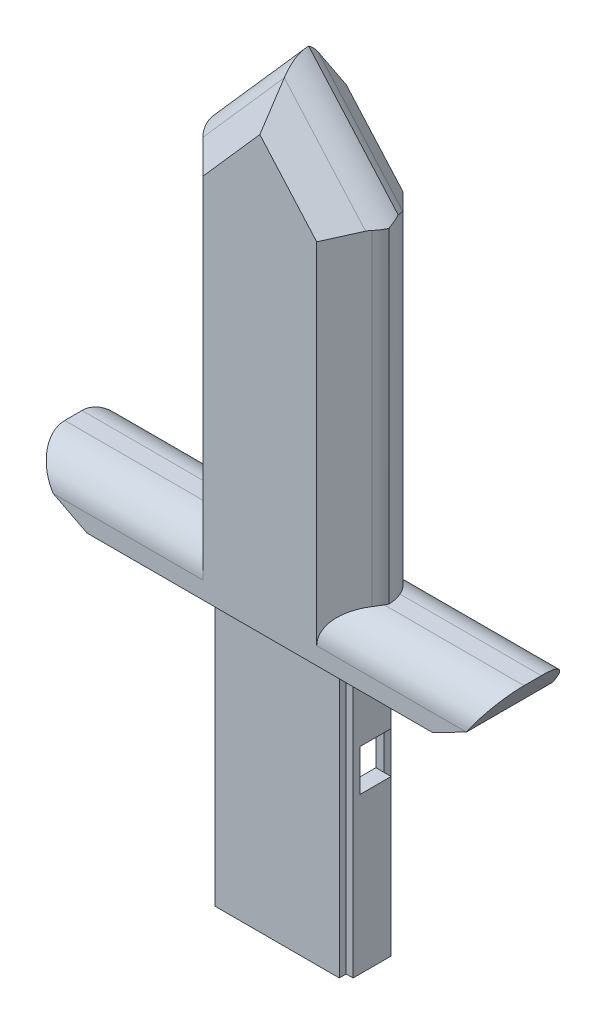
SolidWorks part; units mm, degrees
ref_plane "前视基准面" through (0, 0, 0) normal (0, 0, 1) x (1, 0, 0)
ref_plane "上视基准面" through (0, 0, 0) normal (0, 1, 0) x (1, 0, 0)
ref_plane "右视基准面" through (0, 0, 0) normal (1, 0, 0) x (0, 0, -1)
other "Configuration Table"
sketch "草图1" plane through (0, 0, 0) normal (0, 0, 1) x (1, 0, 0)
  line L0 (0, -55) -> (0, 55) construction
  line L1 (0, 200) -> (-26.4575, 170)
  line L2 (-26.4575, 170) -> (-26.4575, 75)
  line L3 (-26.4575, 75) -> (-66.4575, 75)
  line L4 (-66.4575, 75) -> (-59.7843, 65.0266)
  line L5 (-59.7843, 65.0266) -> (-50, 60)
  line L7 (-50, 60) -> (-20, 60)
  line L9 (-20, 60) -> (-20, -20)
  line L10 (-20, -20) -> (20, -20)
  line L11 (0, 200) -> (0, -20)
  line L15 (-26.4575, 170) -> (26.4575, 170) construction
  line L18 (20, 60) -> (20, -20)
  line L19 (50, 60) -> (20, 60)
  line L20 (59.7843, 65.0266) -> (50, 60)
  line L21 (66.4575, 75) -> (59.7843, 65.0266)
  line L22 (26.4575, 75) -> (66.4575, 75)
  line L23 (26.4575, 170) -> (26.4575, 75)
  line L24 (0, 200) -> (26.4575, 170)
  point P18 (0, 170)
  dimension "D1" = 80
  dimension "D2" = 20
  dimension "D3" = 220
  dimension "D4" = 40
  dimension "D5" = 95
  dimension "D6" = 15
  dimension "D7" = 30
  dimension "D8" = 40
  dimension "D9" = 12
  dimension "D10" = 11
  dimension "D11" = 20
extrude "凸台-拉伸1" add sketch "草图1" along normal blind 15 contours L1 L15 L11 | L11 L15 L24 | L15 L2 L3 L4 L5 L7 L9 L10 L11 | L15 L11 L10 L18 L19 L20 L21 L22 L23
sketch "草图2" plane through (0, 0, 0) normal (0, 0, -1) x (-1, 0, 0)
  line L0 (0, 81.7011) -> (-15, 66.7011)
  line L1 (-15, 66.7011) -> (0, 51.7011)
  line L2 (0, 51.7011) -> (15, 66.7011)
  line L3 (15, 66.7011) -> (0, 81.7011)
  dimension "D1" = 30
  dimension "D4" = 51.7011
extrude "切除-拉伸4" cut sketch "草图2" against normal through all
sketch "草图4" plane through (0, 0, 0) normal (0, 0, -1) x (-1, 0, 0)
  line L0 (-15, 66.7011) -> (-15, -15)
  line L1 (-15, -15) -> (15, -15)
  line L2 (15, -15) -> (15, 66.7011)
  line L3 (20, -20) -> (-20, -20) construction
  line M6 (15, 66.7011) -> (0, 51.7011)
  line M7 (0, 51.7011) -> (-15, 66.7011)
  dimension "D1" = 5
extrude "切除-拉伸5" cut sketch "草图4" against normal blind 5 and the other way through all contours L1 L2 L0 M6 M7
sketch "草图5" plane through (0, 0, 0) normal (0, 0, 1) x (1, 0, 0)
  line L0 (0, 200) -> (26.4575, 170)
  line L1 (26.4575, 170) -> (26.4575, 75)
  line L2 (26.4575, 75) -> (66.4575, 75)
  line L3 (66.4575, 75) -> (59.7843, 65.0266)
  line L4 (59.7843, 65.0266) -> (50, 60)
  line L5 (50, 60) -> (20, 60)
  line L6 (20, 60) -> (-20, 60)
  line L7 (-20, 60) -> (-50, 60)
  line L8 (-50, 60) -> (-59.7843, 65.0266)
  line L9 (-59.7843, 65.0266) -> (-66.4575, 75)
  line L10 (-66.4575, 75) -> (-26.4575, 75)
  line L11 (-26.4575, 75) -> (-26.4575, 170)
  line L12 (-26.4575, 170) -> (0, 200)
extrude "凸台-拉伸2" add sketch "草图5" against normal blind 5
sketch "草图7" plane through (0, 0, 0) normal (0, 0, 1) x (1, 0, 0)
  line L0 (0, 81.7011) -> (-15, 66.7011)
  line L1 (-15, 66.7011) -> (-15, 60)
  line L2 (-15, 60) -> (15, 60) construction
  line L3 (-15, 60) -> (15, 60)
  line L4 (15, 60) -> (15, 66.7011)
  line L5 (15, 66.7011) -> (0, 81.7011)
extrude "切除-拉伸6" cut sketch "草图7" against normal blind 5
sketch "草图8" plane through (0, 0, 5) normal (0, 0, -1) x (-1, 0, 0)
  line L0 (-15, 66.7011) -> (0, 51.7011)
  line L1 (0, 51.7011) -> (15, 66.7011)
  line L2 (15, 66.7011) -> (15, -15)
  line L3 (15, -15) -> (-15, -15)
  line L4 (-15, -15) -> (-15, 66.7011)
extrude "切除-拉伸7" cut sketch "草图8" against normal blind 5
sketch "草图9" plane through (0, -20, 0) normal (0, -1, 0) x (1, 0, 0)
  line L0 (15, 4) -> (15, 7)
  line L1 (15, 7) -> (-15, 7)
  line L2 (-15, 7) -> (-15, 4)
  line L3 (-15, 4) -> (15, 4)
  line L4 (-20, 0) -> (20, 0) construction
  line L5 (20, 15) -> (20, 0) construction
  line L6 (-20, 15) -> (-20, 0) construction
  line L7 (-20, 15) -> (20, 15) construction
  dimension "D1" = 4
  dimension "D2" = 5
  dimension "D3" = 5
  dimension "D4" = 8
extrude "切除-拉伸8" cut sketch "草图9" against normal blind 5
sketch "草图10" plane through (0, 0, -5) normal (0, 0, -1) x (-1, 0, 0)
  line L0 (-15, 66.7011) -> (-15, 116.7011)
  line L1 (-15, 116.7011) -> (15, 116.7011)
  line L2 (15, 116.7011) -> (15, 66.7011)
  line L3 (15, 66.7011) -> (-15, 66.7011)
  dimension "D1" = 50
extrude "切除-拉伸9" cut sketch "草图10" against normal up to surface (15 mm away) up to face at (0, 31.0207, 10)
sketch "草图11" plane through (0, 60, 0) normal (0, -1, 0) x (1, 0, 0)
  line L0 (17.5, -1.5) -> (15, -1.5)
  line L2 (15, -5) -> (15, 0) construction
  line L3 (15, -1.5) -> (15, -5)
  line L4 (15, -5) -> (-15, -5)
  line L5 (-15, -5) -> (-15, -1.5)
  line L6 (-15, -5) -> (-15, 0) construction
  line L7 (-15, -1.5) -> (-17.5, -1.5)
  line L8 (-17.5, -1.5) -> (-17.5, 0)
  line L9 (-20, 0) -> (-15, 0) construction
  line L10 (-17.5, 0) -> (17.5, 0)
  line L11 (17.5, 0) -> (17.5, -1.5)
  dimension "D1" = 1.5
  dimension "D2" = 1.5
  dimension "D3" = 2.5
  dimension "D4" = 2.5
extrude "切除-拉伸10" cut sketch "草图11" against normal up to surface (56.7011 mm away) up to face at (0, 116.7011, 2.5)
sketch "草图12" plane through (0, 0, 10) normal (0, 0, -1) x (-1, 0, 0)
sketch "草图13" plane through (0, 0, 10) normal (0, 0, -1) x (-1, 0, 0)
  line L0 (-20, 121.7011) -> (-20, 71.7011)
  line L1 (-20, 71.7011) -> (20, 71.7011)
  line L2 (20, 71.7011) -> (20.5279, 121.7011)
  line L3 (20.5279, 121.7011) -> (-20, 121.7011)
  dimension "D1" = 40
  dimension "D2" = 50
  dimension "D3" = 10
  dimension "D4" = 20
extrude "切除-拉伸11" cut sketch "草图13" along normal blind 7
sketch "草图14" plane through (0, 0, -5) normal (0, 0, -1) x (-1, 0, 0)
  line L0 (15, 116.7011) -> (-15, 116.7011) construction
  line L1 (-15.6, 116.7011) -> (15.6, 116.7011)
  line L2 (-15.6, 116.7011) -> (-15.6, -14.9949)
  line L3 (-15.6, -14.9949) -> (15.6, -14.9949)
  line L4 (15.6, 116.7011) -> (15.6, -14.9949)
  line L5 (-15, 60) -> (-15, 116.7011) construction
  line L6 (15, 116.7011) -> (15, 60) construction
  dimension "D1" = 0.6
  dimension "D2" = 0.6
  dimension "D3" = 131.6961
extrude "切除-拉伸12" cut sketch "草图14" against normal up to surface (15 mm away) up to face at (0, 31.0207, 10)
sketch "草图15" plane through (0, 71.7011, 0) normal (0, 1, 0) x (1, 0, 0)
  line L0 (-20, -10) -> (20, -10)
  line L1 (-20, -10) -> (-20, -3)
  line L2 (-20, -3) -> (-20, -10) construction
  line L3 (-20, -3) -> (20, -3)
  line L4 (20, -3) -> (20, -10)
  dimension "D1" = 7
extrude "切除-拉伸14" cut sketch "草图15" against normal blind 9
sketch "草图16" plane through (0, 0, 10) normal (0, 0, -1) x (-1, 0, 0)
  line L0 (0, 83.1153) -> (-16.4142, 66.7011)
  line L1 (-16.4142, 66.7011) -> (0, 50.2869)
  line L2 (0, 50.2869) -> (16.4142, 66.7011)
  line L3 (16.4142, 66.7011) -> (0, 83.1153)
  line L4 (-15, 66.7011) -> (0, 81.7011) construction
  line L5 (0, 81.7011) -> (15, 66.7011) construction
  line L6 (15, 66.7011) -> (0, 51.7011) construction
  line L7 (0, 51.7011) -> (-15, 66.7011) construction
  dimension "D1" = 1
  dimension "D2" = 1
  dimension "D3" = 1
  dimension "D4" = 1
extrude "切除-拉伸15" cut sketch "草图16" against normal through all
sketch "草图17" plane through (0, 0, 15) normal (0, 0, 1) x (1, 0, 0)
  line L0 (0, 83.1153) -> (-16.4142, 66.7011)
  line L1 (-16.4142, 66.7011) -> (0, 50.2869)
  line L2 (0, 50.2869) -> (16.4142, 66.7011)
  line L3 (16.4142, 66.7011) -> (0, 83.1153)
extrude "凸台-拉伸3" add sketch "草图17" against normal up to surface (5 mm away) up to face at (0, 66.7011, 10)
sketch "草图18" plane through (0, 0, 15) normal (0, 0, 1) x (1, 0, 0)
  line L0 (-20, 60) -> (20, 60)
  line L1 (20, 60) -> (20, -20)
  line L2 (20, -20) -> (-20, -20)
  line L3 (-20, -20) -> (-20, 60)
sketch "草图19" plane through (0, 0, 15) normal (0, 0, 1) x (1, 0, 0)
  line L0 (-26.4575, 75) -> (26.4575, 75)
  line L1 (0, 200) -> (0, 75)
sketch "草图23" plane through (-26.4575, 0, 0) normal (-1, 0, 0) x (0, 0, 1)
  line L0 (-5, 75) -> (15, 75)
  line L1 (5, 75) -> (5, 82.7603) construction
sketch "草图24" plane through (26.4575, 0, 0) normal (1, 0, 0) x (0, 0, -1)
  line L0 (-15, 75) -> (5, 75)
  line L1 (-5, 75) -> (-5, 85.0123) construction
sketch "草图26" plane through (0, 0, 15) normal (0, 0, 1) x (1, 0, 0)
  line L0 (0, 200) -> (-26.4575, 170)
  line L1 (-26.4575, 170) -> (-26.4575, 75)
  line L2 (-26.4575, 75) -> (-66.4575, 75)
  line L3 (-66.4575, 75) -> (-59.7843, 65.0266)
  line L4 (-59.7843, 65.0266) -> (-50, 60)
  line L5 (-50, 60) -> (-20, 60)
  line L6 (-20, 60) -> (50, 60)
  line L7 (50, 60) -> (59.7843, 65.0266)
  line L8 (59.7843, 65.0266) -> (66.4575, 75)
  line L9 (66.4575, 75) -> (26.4575, 75)
  line L10 (26.4575, 75) -> (26.4575, 170)
  line L11 (26.4575, 170) -> (0, 200)
extrude "凸台-拉伸4" add sketch "草图26" along normal blind 5
sketch "草图27" plane through (0, -20, 0) normal (0, -1, 0) x (1, 0, 0)
  line L2 (-20, 15) -> (-18, 15)
  line L3 (20, 15) -> (-20, 15) construction
  line L4 (-18, 15) -> (-18, 13)
  line L5 (-18, 13) -> (-20, 13)
  line L6 (-20, 15) -> (-20, 0) construction
  line L7 (-20, 13) -> (-20, 15)
  line L8 (-20, 0) -> (-18, 0)
  line L9 (-20, 0) -> (20, 0) construction
  line L10 (-18, 0) -> (-18, 2)
  line L11 (-18, 2) -> (-20, 2)
  line L12 (-20, 2) -> (-20, 0)
  line L13 (20, 15) -> (20, 13)
  line L14 (20, 15) -> (20, 0) construction
  line L15 (20, 13) -> (18, 13)
  line L16 (18, 13) -> (18, 15)
  line L17 (18, 15) -> (20, 15)
  line L18 (20, 0) -> (18, 0)
  line L19 (18, 0) -> (18, 2)
  line L20 (18, 2) -> (20, 2)
  line L21 (20, 2) -> (20, 0)
  dimension "D1" = 2
  dimension "D2" = 2
  dimension "D3" = 2
  dimension "D4" = 2
  dimension "D5" = 2
  dimension "D6" = 2
  dimension "D7" = 2
  dimension "D8" = 2
extrude "切除-拉伸17" cut sketch "草图27" against normal blind 80
sketch "草图29" plane through (0, -20, 0) normal (0, -1, 0) x (-1, 0, 0)
  line L0 (15, -7) -> (15, -4)
  line L1 (15, -4) -> (-15, -4)
  line L2 (-15, -4) -> (-15, -7)
  line L3 (-15, -7) -> (15, -7)
extrude "凸台-拉伸5" add sketch "草图29" against normal up to surface (5 mm away) up to face at (0, -15, 8.5)
sketch "草图30" plane through (15.6, 0, 0) normal (-1, 0, 0) x (0, 0, 1)
  line L0 (2, 25.0051) -> (10, 25.0051)
  line L2 (10, -14.9949) -> (10, 62.7011) construction
  line L3 (10, 25.0051) -> (10, 37.0051)
  line L4 (10, 37.0051) -> (2, 37.0051)
  line L5 (2, 37.0051) -> (2, 25.0051)
  line L6 (10, -14.9949) -> (0, -14.9949) construction
  dimension "D1" = 40
  dimension "D2" = 12
  dimension "D3" = 8
extrude "切除-拉伸19" cut sketch "草图30" against normal up to surface (4.4 mm away) up to face at (20, 20, 7.5)
sketch "草图31" plane through (15.6, 0, 0) normal (-1, 0, 0) x (0, 0, 1)
  line L0 (10, 35.0051) -> (2, 35.0051)
  line L1 (10, 37.0051) -> (10, 62.7011) construction
  line L2 (2, 35.0051) -> (2, 44.0051)
  line L3 (2, 44.0051) -> (10, 44.0051)
  line L4 (10, 44.0051) -> (10, 35.0051)
  line L5 (10, -14.9949) -> (0, -14.9949) construction
  dimension "D1" = 8
  dimension "D2" = 50
  dimension "D3" = 9
sketch "草图32" plane through (0, 60, 0) normal (0, -1, 0) x (1, 0, 0)
  line L0 (-18, 15) -> (18, 15) construction
  line L1 (-22.4, 17.4) -> (22.4, 17.4)
  line L2 (-22.4, 17.4) -> (-22.4, -2.4)
  line L3 (-22.4, -2.4) -> (22.4, -2.4)
  line L4 (22.4, 17.4) -> (22.4, -2.4)
  line L5 (-20, 13) -> (-20, 2) construction
  dimension "D1" = 44.8
  dimension "D2" = 19.8
  dimension "D3" = 2.4
  dimension "D4" = 2.4
extrude "切除-拉伸21" cut sketch "草图32" against normal blind 5
sketch "草图35" plane through (0, 65, 0) normal (0, -1, 0) x (1, 0, 0)
  line L0 (-50, 20) -> (50, 20)
  line L1 (50, 20) -> (50, -5)
  line L2 (50, -5) -> (-50, -5)
  line L3 (-50, -5) -> (-50, 20)
  line L5 (25, -1.5) -> (-25, -1.5)
  line L6 (25, -1.5) -> (25, 16.5)
  line L7 (25, 16.5) -> (-25, 16.5)
  line L8 (-25, -1.5) -> (-25, 16.5)
  line L11 (20, 10) -> (20, 3) construction
  line L13 (15.5816, -5) -> (15.6, -1.5)
  line L14 (-15.6, -5) -> (-15.6, -1.5)
  line M6 (-15.6, -5) -> (-15.6, -1.5)
  line M7 (-15.6, -1.5) -> (-17.5, -1.5)
  line M27 (17.5, -1.5) -> (15.6, -1.5)
  line M28 (15.6, -1.5) -> (15.6, -5)
  line M29 (15.6, -5) -> (50, -5)
  line M30 (50, -5) -> (50, 20)
  line M31 (50, 20) -> (-50, 20)
  line M32 (-50, 20) -> (-50, -5)
  line M33 (-50, -5) -> (-15.6, -5)
  dimension "D1" = 18
  dimension "D2" = 3.5
  dimension "D3" = 50
  dimension "D4" = 5
extrude "凸台-拉伸7" add sketch "草图35" along normal blind 5 contours L5 L8 L7 L6 M27 M28 M29 M30 M31 M32 M33 M6 M7
sketch "草图36" plane through (0, 65, 0) normal (0, -1, 0) x (1, 0, 0)
  line L0 (25, -1.5) -> (25, 16.5)
  line L1 (25, 16.5) -> (-25, 16.5)
  line L2 (-25, 16.5) -> (-25, -1.5)
  line L3 (-25, -1.5) -> (25, -1.5)
  line M1 (-25, 16.5) -> (-25, -1.5)
  line M2 (-25, -1.5) -> (-17.5, -1.5)
  line M3 (-17.5, -1.5) -> (-17.5, 0)
  line M4 (-17.5, 0) -> (-18, 0)
  line M5 (-18, 0) -> (-18, 2)
  line M6 (-18, 2) -> (-20, 2)
  line M7 (-20, 2) -> (-20, 3)
  line M8 (-20, 3) -> (-20, 10)
  line M9 (-20, 10) -> (-20, 13)
  line M10 (-20, 13) -> (-18, 13)
  line M11 (-18, 13) -> (-18, 15)
  line M12 (-18, 15) -> (18, 15)
  line M13 (18, 15) -> (18, 13)
  line M14 (18, 13) -> (20, 13)
  line M15 (20, 13) -> (20, 10)
  line M16 (20, 10) -> (20, 3)
  line M17 (20, 3) -> (20, 2)
  line M18 (20, 2) -> (18, 2)
  line M19 (18, 2) -> (18, 0)
  line M20 (18, 0) -> (17.5, 0)
  line M21 (17.5, 0) -> (17.5, -1.5)
  line M22 (17.5, -1.5) -> (25, -1.5)
  line M23 (25, -1.5) -> (25, 16.5)
  line M24 (25, 16.5) -> (-25, 16.5)
extrude "凸台-拉伸9" add sketch "草图36" along normal blind 2 contours M24 M1 M2 M3 M4 M5 M6 M7 M8 M9 M10 M11 M12 M13 M14 M15 M16 M17 M18 M19 M20 M21 M22 M23
sketch "草图37" plane through (0, 63, 0) normal (0, -1, 0) x (-1, 0, 0)
  line L0 (25, -16.5) -> (25, 1.5) construction
  line L1 (-25, -16.5) -> (25, -16.5) construction
  line L2 (25, 1.5) -> (17.5, 1.5) construction
  line L3 (-25, 1.5) -> (-25, -16.5) construction
  line L4 (-25, -16.5) -> (25, -16.5) construction
  line L5 (-17.5, 1.5) -> (-25, 1.5) construction
  circle A0 centre (22.5, -14) radius 1.2
  circle A1 centre (-22.5, -14) radius 1.2
  circle A2 centre (-22.5, -1) radius 1.2
  circle A3 centre (22.5, -1) radius 1.2
  dimension "D1" = 2.4
  dimension "D4" = 2.4
  dimension "D10" = 2.4
  dimension "D11" = 2.4
  dimension "D2" = 2.5
  dimension "D3" = 2.5
  dimension "D5" = 2.5
  dimension "D6" = 2.5
  dimension "D7" = 2.5
  dimension "D8" = 2.5
  dimension "D9" = 2.5
  dimension "D12" = 2.5
chamfer "倒角1" distance 10 angle 45 1 edges at (-13.2288, 185, -5)
chamfer "倒角2" distance 10 angle 45 1 edges at (16.5621, 181.2204, -5)
chamfer "倒角3" distance 10 angle 45 1 edges at (13.2288, 185, 20)
chamfer "倒角4" distance 10 angle 45 1 edges at (-16.5621, 181.2204, 20)
chamfer "倒角5" distance 10 angle 45 1 edges at (26.4575, 114.9407, 20)
chamfer "倒角6" distance 10 angle 45 1 edges at (26.4575, 114.9407, -5)
chamfer "倒角7" distance 10 angle 45 1 edges at (-26.4575, 114.9407, -5)
chamfer "倒角8" distance 10 angle 45 1 edges at (-26.4575, 114.9407, 20)
fillet "圆角7" radius 10 1 edges at (41.4575, 75, 20)
fillet "圆角8" radius 10 1 edges at (41.4575, 75, -5)
fillet "圆角9" radius 10 1 edges at (-41.4575, 75, -5)
fillet "圆角10" radius 10 1 edges at (-41.4575, 75, 20)
fillet "圆角11" radius 10 1 edges at (26.4575, 122.5, 5)
fillet "圆角12" radius 10 1 edges at (26.4575, 122.5, 10)
fillet "圆角14" radius 10 1 edges at (13.0034, 185.2555, 10)
fillet "圆角15" radius 10 1 edges at (12.7797, 185.5092, 5)
fillet "圆角16" radius 10 1 edges at (-13.5282, 184.6605, 10)
fillet "圆角17" radius 10 1 edges at (-13.379, 184.8296, 5)
fillet "圆角18" radius 10 1 edges at (-26.4575, 121.821, 10)
fillet "圆角19" radius 10 1 edges at (-26.4575, 122.1593, 5)
sketch "草图38" plane through (0, 0, 10) normal (0, 0, -1) x (-1, 0, 0)
  line L2 (15.6, 62.7011) -> (15.6, -14.9949) construction
  line L3 (-15, -15) -> (15, -15) construction
  circle A0 centre (-11.9, 20.2) radius 1.2
  circle A1 centre (12.3, 20.2) radius 1.2
  circle A2 centre (12.3, 57) radius 1.2
  circle A3 centre (-11.9, 57) radius 1.2
  dimension "D1" = 2.4
  dimension "D2" = 2.4
  dimension "D3" = 2.4
  dimension "D4" = 2.4
  dimension "D5" = 24.2
  dimension "D6" = 24.2
  dimension "D7" = 3.3
  dimension "D8" = 3.3
  dimension "D9" = 35.2
  dimension "D10" = 35.2
  dimension "D11" = 72
  dimension "D12" = 72
extrude "切除-拉伸23" cut sketch "草图38" against normal blind 3
sketch "草图39" plane through (0, 0, 10) normal (0, 0, -1) x (-1, 0, 0)
  line L0 (-15.6, -14.9949) -> (-15.6, 81.8297)
  line L1 (-15.6, 81.8297) -> (15.6, 81.8297)
  line L2 (15.6, 81.8297) -> (15.6, -14.9949)
  line L3 (15.6, -14.9949) -> (-15.6, -14.9949)
sketch "草图40" plane through (0, 121.7011, 0) normal (0, -1, 0) x (1, 0, 0)
  line L1 (-25.4676, 12.5781) -> (26.0169, 12.5781)
  line L2 (-25.4676, 12.5781) -> (-25.4676, 0.933)
  line L3 (-25.4676, 0.933) -> (26.0169, 0.933)
  line L4 (26.0169, 12.5781) -> (26.0169, 0.933)
  line M5 (20, 10) -> (-20.5279, 10)
  line M6 (-20.5279, 10) -> (-20.5279, 3)
  line M7 (-20.5279, 3) -> (20, 3)
  line M8 (20, 3) -> (20, 10)
extrude "切除-拉伸24" cut sketch "草图40" against normal blind 8 contours M8 M5 M6 M7
sketch "草图41" plane through (0, 116.7011, 0) normal (0, -1, 0) x (1, 0, 0)
  line L1 (21.831, -9.4178) -> (-23.2428, -9.4178)
  line L2 (21.831, -9.4178) -> (21.831, 6.3066)
  line L3 (21.831, 6.3066) -> (-23.2428, 6.3066)
  line L4 (-23.2428, -9.4178) -> (-23.2428, 6.3066)
  line M5 (-15.6, -5) -> (15.6, -5)
  line M6 (15.6, -5) -> (15.6, -1.5)
  line M7 (15.6, -1.5) -> (17.5, -1.5)
  line M8 (17.5, -1.5) -> (17.5, 0)
  line M9 (17.5, 0) -> (15.6, 0)
  line M10 (15.6, 0) -> (15.6, 3)
  line M11 (15.6, 3) -> (-15.6, 3)
  line M12 (-15.6, 3) -> (-15.6, 0)
  line M13 (-15.6, 0) -> (-17.5, 0)
  line M14 (-17.5, 0) -> (-17.5, -1.5)
  line M15 (-17.5, -1.5) -> (-15.6, -1.5)
  line M16 (-15.6, -1.5) -> (-15.6, -5)
extrude "切除-拉伸25" cut sketch "草图41" against normal blind 46 contours M16 M5 M6 M7 M8 M9 M10 M11 M12 M13 M14 M15
sketch "草图42" plane through (0, 129.7011, 0) normal (0, -1, 0) x (1, 0, 0)
  line L1 (-35.652, 24.0881) -> (44.2679, 24.0881)
  line L2 (-35.652, 24.0881) -> (-35.652, -20.2789)
  line L3 (-35.652, -20.2789) -> (44.2679, -20.2789)
  line L4 (44.2679, 24.0881) -> (44.2679, -20.2789)
  line M5 (20, 3) -> (20, 10)
  line M6 (20, 10) -> (-20.5279, 10)
  line M7 (-20.5279, 10) -> (-20.5279, 3)
  line M8 (-20.5279, 3) -> (-15.6, 3)
  line M9 (-15.6, 3) -> (15.6, 3)
  line M10 (15.6, 3) -> (20, 3)
extrude "切除-拉伸26" cut sketch "草图42" against normal up to surface (33 mm away) contours M10 M5 M6 M7 M8 M9 up to face at (0, 162.7011, -0.8333)
sketch "草图43" plane through (0, 0, 10) normal (0, 0, -1) x (-1, 0, 0)
  line L0 (-15.6, 15.2) -> (15.6, 15.2)
  line L1 (-10.6, 106.2) -> (10.6, 106.2)
  line L2 (-10.6, 106.2) -> (-10.6, 84.2)
  line L3 (-10.6, 84.2) -> (10.6, 84.2)
  line L4 (10.6, 106.2) -> (10.6, 84.2)
  line L5 (-15.6, -14.9949) -> (-15.6, 25.0051) construction
  line L6 (15.6, 62.7011) -> (15.6, -14.9949) construction
  line L7 (-15.6, 37.0051) -> (-15.6, 62.7011) construction
  circle A0 centre (-11.9, 20.2) radius 1.2 construction
  dimension "D1" = 5
  dimension "D2" = 69
  dimension "D3" = 91
  dimension "D4" = 5
  dimension "D5" = 5
extrude "切除-拉伸27" cut sketch "草图43" against normal up to surface (10 mm away) contours L4 L1 L2 L3 up to face at (0, 99.7025, 20)
sketch "草图46" plane through (0, 60, 0) normal (0, -1, 0) x (1, 0, 0)
  line L1 (-27.4, 17.4) -> (27.4, 17.4)
  line L2 (-27.4, 17.4) -> (-27.4, -2.4)
  line L3 (-27.4, -2.4) -> (27.4, -2.4)
  line L4 (27.4, 17.4) -> (27.4, -2.4)
  line L6 (-20, 10) -> (-20, 13) construction
  line L8 (-18, 15) -> (18, 15) construction
  line M5 (-15.6, -1.5) -> (-25, -1.5)
  line M6 (-25, -1.5) -> (-25, 16.5)
  line M7 (-25, 16.5) -> (25, 16.5)
  line M8 (25, 16.5) -> (25, -1.5)
  line M9 (25, -1.5) -> (15.6, -1.5)
  line M10 (15.6, -1.5) -> (15.6, -5)
  line M16 (-15.6, -5) -> (-15.6, -1.5)
  dimension "D1" = 19.8
  dimension "D2" = 54.8
  dimension "D3" = 7.4
  dimension "D4" = 2.4
extrude "切除-拉伸28" cut sketch "草图46" against normal up to surface (3 mm away) contours L4 L1 L2 L3 M16 M5 M6 M7 M8 M9 M10 up to face at (0, 63, 5.9583)
sketch "草图47" plane through (0, 63, 0) normal (0, -1, 0) x (1, 0, 0)
  line L0 (27.4, 17.4) -> (-27.4, 17.4) construction
  line L1 (-27.4, -2.4) -> (-27.4, 17.4) construction
  line L3 (-15.6, -2.4) -> (-27.4, -2.4) construction
  line L4 (27.4, -2.4) -> (27.4, 17.4) construction
  line L5 (27.4, -2.4) -> (15.6, -2.4) construction
  line L6 (27.4, 17.4) -> (27.4, -2.4) construction
  circle A0 centre (-24.9, 14.9) radius 1.2
  circle A1 centre (24.9, 14.9) radius 1.2
  circle A2 centre (24.9, 0.1) radius 1.2
  circle A3 centre (-24.9, 0.1) radius 1.2
  dimension "D3" = 2.4
  dimension "D6" = 2.4
  dimension "D9" = 2.4
  dimension "D12" = 2.4
  dimension "D1" = 2.5
  dimension "D2" = 2.5
  dimension "D4" = 2.5
  dimension "D5" = 2.5
  dimension "D7" = 2.5
  dimension "D8" = 2.5
  dimension "D10" = 2.5
  dimension "D11" = 2.5
extrude "切除-拉伸29" cut sketch "草图47" against normal blind 3
sketch "草图48" plane through (0, 62.7011, 0) normal (0, 1, 0) x (1, 0, 0)
  line L1 (-26.5409, 2.5519) -> (32.582, 2.5519)
  line L2 (-26.5409, 2.5519) -> (-26.5409, -20.82)
  line L3 (-26.5409, -20.82) -> (32.582, -20.82)
  line L4 (32.582, 2.5519) -> (32.582, -20.82)
  line M1 (-15.6, -3) -> (-20, -3)
  line M2 (-20, -3) -> (-20, -10)
  line M3 (-20, -10) -> (-15.6, -10)
  line M4 (-15.6, -10) -> (-15.6, -3)
extrude "凸台-拉伸10" add sketch "草图48" along normal blind 9 contours M4 M1 M2 M3
sketch "草图49" plane through (0, 62.7011, 0) normal (0, 1, 0) x (1, 0, 0)
  line L1 (8.4178, 4.2355) -> (27.2342, 4.2355)
  line L2 (8.4178, 4.2355) -> (8.4178, -17.2548)
  line L3 (8.4178, -17.2548) -> (27.2342, -17.2548)
  line L4 (27.2342, 4.2355) -> (27.2342, -17.2548)
  line M1 (15.6, -10) -> (20, -10)
  line M2 (20, -10) -> (20, -3)
  line M3 (20, -3) -> (15.6, -3)
  line M4 (15.6, -3) -> (15.6, -10)
extrude "凸台-拉伸11" add sketch "草图49" along normal blind 9 contours M4 M1 M2 M3
sketch "草图50" plane through (0, 0, 10) normal (0, 0, -1) x (-1, 0, 0)
  line L1 (-63.6393, 193.626) -> (75.0944, 193.626)
  line L2 (-63.6393, 193.626) -> (-63.6393, -29.1115)
  line L3 (-63.6393, -29.1115) -> (75.0944, -29.1115)
  line L4 (75.0944, 193.626) -> (75.0944, -29.1115)
  circle M5 centre (-11.9, 57) radius 1.2
  circle M6 centre (12.3, 57) radius 1.2
  circle M7 centre (12.3, 20.2) radius 1.2
  circle M8 centre (-11.9, 20.2) radius 1.2
  line M9 (-10.6, 106.2) -> (10.6, 106.2)
  line M10 (10.6, 106.2) -> (10.6, 84.2)
  line M11 (10.6, 84.2) -> (-10.6, 84.2)
  line M12 (-10.6, 84.2) -> (-10.6, 106.2)
  line M13 (-20, 71.7011) -> (-15.6, 71.7011)
  line M14 (-15.6, 71.7011) -> (-15.6, 37.0051)
  line M15 (-15.6, 37.0051) -> (-20, 37.0051)
  line M16 (-20, 37.0051) -> (-20, 25.0051)
  line M17 (-20, 25.0051) -> (-15.6, 25.0051)
  line M18 (-15.6, 25.0051) -> (-15.6, -14.9949)
  line M19 (-15.6, -14.9949) -> (-15, -14.9949)
  line M20 (-15, -14.9949) -> (-15, -15)
  line M21 (-15, -15) -> (15, -15)
  line M22 (15, -15) -> (15, -14.9949)
  line M23 (15, -14.9949) -> (15.6, -14.9949)
  line M24 (15.6, -14.9949) -> (15.6, 71.7011)
  line M25 (15.6, 71.7011) -> (20, 71.7011)
  line M26 (20, 71.7011) -> (20.5279, 121.7011)
  line M27 (20.5279, 121.7011) -> (20.5279, 162.7011)
  line M28 (20.5279, 162.7011) -> (-20, 162.7011)
  line M29 (-20, 162.7011) -> (-20, 71.7011)
extrude "切除-拉伸30" cut sketch "草图50" against normal blind 1 contours M29 M13 M14 M15 M16 M17 M18 M19 M20 M21 M22 M23 M24 M25 M26 M27 M28 M6 M8 M12 M9 M10 M11 M7 M5
sketch "草图52" plane through (0, 0, 20) normal (0, 0, 1) x (1, 0, 0)
  line L0 (-2.5, 99.2) -> (-2.5, 91.2)
  line L1 (-2.5, 91.2) -> (2.5, 91.2)
  line L2 (2.5, 91.2) -> (2.5, 99.2)
  line L3 (2.5, 99.2) -> (-2.5, 99.2)
  line L6 (10.6, 106.2) -> (-10.6, 106.2) construction
  line L7 (-10.6, 106.2) -> (-10.6, 84.2) construction
  line M12 (10.6, 84.2) -> (-10.6, 84.2)
  line M13 (-10.6, 84.2) -> (-10.6, 106.2)
  line M14 (-10.6, 106.2) -> (10.6, 106.2)
  line M15 (10.6, 106.2) -> (10.6, 84.2)
  dimension "D1" = 5
  dimension "D2" = 8
  dimension "D3" = 7
  dimension "D4" = 8.1
extrude "凸台-拉伸12" add sketch "草图52" against normal blind 2 contours L3 L2 L1 L0 M12 M15 M14 M13
sketch "草图53" plane through (0, 0, 11) normal (0, 0, -1) x (-1, 0, 0)
  line L0 (-10, 79.2) -> (-10, 61.2)
  line L1 (-10, 61.2) -> (10, 61.2)
  line L2 (10, 61.2) -> (10, 79.2)
  line L3 (10, 79.2) -> (-10, 79.2)
  line L4 (-15.6, 71.7011) -> (-15.6, 37.0051) construction
  line L6 (10.6, 84.2) -> (-10.6, 84.2) construction
  dimension "D1" = 20
  dimension "D2" = 18
  dimension "D3" = 5.6
  dimension "D4" = 5
extrude "切除-拉伸31" cut sketch "草图53" against normal blind 2
sketch "草图54" plane through (0, 162.7011, 0) normal (0, -1, 0) x (1, 0, 0)
  line L0 (-15.6, 3) -> (15.6, 3)
  line L2 (-27.0309, 16.3139) -> (27.2462, 16.3139)
  line L3 (-27.0309, 16.3139) -> (-27.0309, 0.5752)
  line L4 (-27.0309, 0.5752) -> (27.2462, 0.5752)
  line L5 (27.2462, 16.3139) -> (27.2462, 0.5752)
  line M9 (15.6, 3) -> (20, 3)
  line M10 (20, 3) -> (20, 11)
  line M11 (20, 11) -> (-20.5279, 11)
  line M12 (-20.5279, 11) -> (-20.5279, 3)
  line M13 (-20.5279, 3) -> (-15.6, 3)
extrude "切除-拉伸33" cut sketch "草图54" against normal blind 6 contours L0 M13 M9 M10 M11 M12
sketch "草图56" plane through (0, 0, 11) normal (0, 0, -1) x (-1, 0, 0)
  line L0 (-10.6, 106.2) -> (10.6, 106.2)
  line L1 (10.6, 106.2) -> (10.6, 84.2)
  line L2 (10.6, 84.2) -> (-10.6, 84.2)
  line L3 (-10.6, 84.2) -> (-10.6, 106.2)
extrude "凸台-拉伸13" add sketch "草图56" against normal up to surface (9 mm away) up to face at (0, 99.7025, 20)
